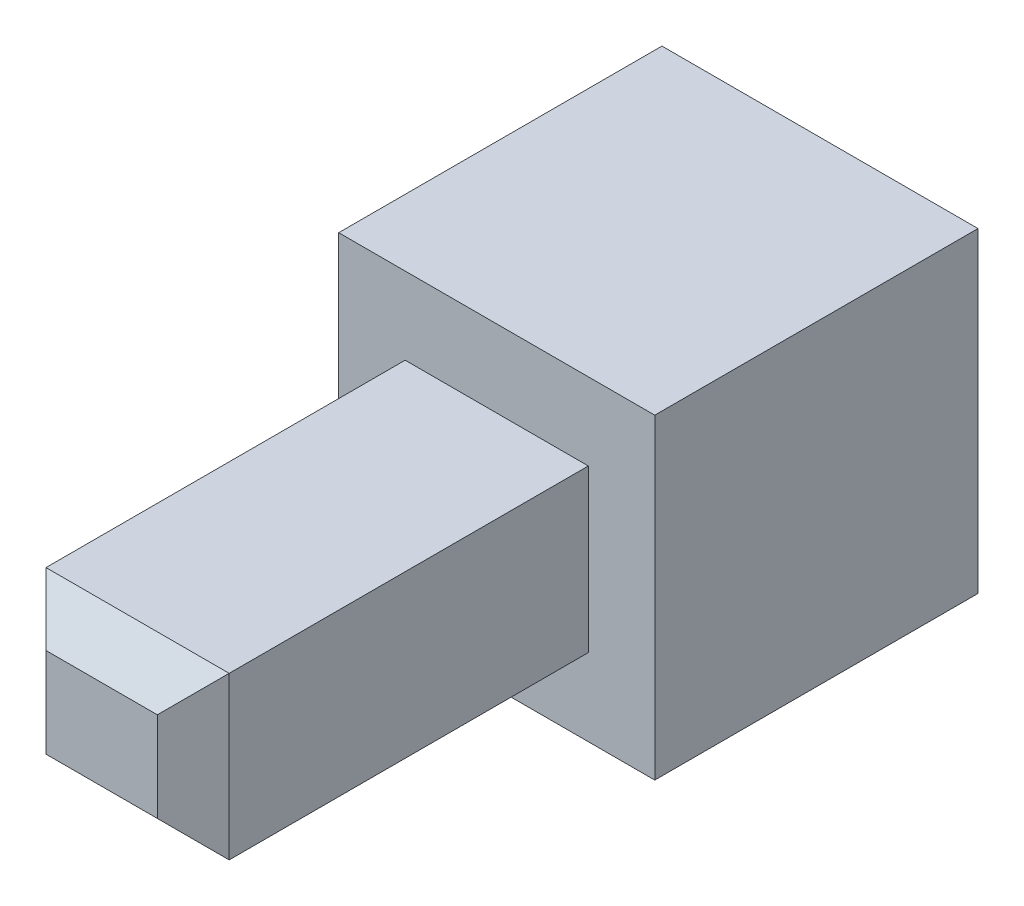
SolidWorks part; units mm, degrees
ref_plane "Front Plane" through (0, 0, 0) normal (0, 0, 1) x (1, 0, 0)
ref_plane "Top Plane" through (0, 0, 0) normal (0, 1, 0) x (1, 0, 0)
ref_plane "Right Plane" through (0, 0, 0) normal (1, 0, 0) x (0, 0, -1)
sketch "Sketch2" plane through (0, 0, -12.4) normal (0, 0, 1) x (1, 0, 0)
  line L0 (-26.1526, 94.1826) -> (-31.3526, 94.1826) construction
  line L1 (-33.1526, 95.6826) -> (-24.3526, 95.6826)
  line L2 (-33.1526, 95.6826) -> (-33.1526, 86.8826)
  line L3 (-33.1526, 86.8826) -> (-24.3526, 86.8826)
  line L4 (-24.3526, 95.6826) -> (-24.3526, 86.8826)
  line L6 (-31.6526, 93.8826) -> (-31.6526, 88.6826) construction
  line L7 (-31.3526, 88.3826) -> (-26.1526, 88.3826) construction
  line L10 (-31.9526, 94.4826) -> (-25.5526, 94.4826)
  line L11 (-31.9526, 94.4826) -> (-31.9526, 88.0826)
  line L12 (-31.9526, 88.0826) -> (-25.5526, 88.0826)
  line L13 (-25.5526, 94.4826) -> (-25.5526, 88.0826)
  dimension "D1" = 1.5
  dimension "D2" = 1.5
  dimension "D3" = 1.5
  dimension "D4" = 1.2
  dimension "D5" = 1.2
  dimension "D6" = 1.2
  dimension "D7" = 1.2
extrude "Boss-Extrude1" add sketch "Sketch2" against normal blind 2 and the other way blind 2
sketch "Sketch3" plane through (0, 0, -10.4) normal (0, 0, 1) x (1, 0, 0)
  line L1 (-33.1526, 95.6826) -> (-24.3526, 95.6826)
  line L2 (-33.1526, 95.6826) -> (-33.1526, 86.8826)
  line L3 (-33.1526, 86.8826) -> (-24.3526, 86.8826)
  line L4 (-24.3526, 95.6826) -> (-24.3526, 86.8826)
extrude "Boss-Extrude2" add sketch "Sketch3" along normal blind 5
sketch "Sketch4" plane through (0, 0, -5.4) normal (0, 0, 1) x (1, 0, 0)
  line L0 (-25.9026, 93.8326) -> (-31.6026, 93.8326) construction
  line L1 (-31.3026, 93.5326) -> (-26.2026, 93.5326)
  line L2 (-31.3026, 93.5326) -> (-31.3026, 89.0326)
  line L3 (-31.3026, 89.0326) -> (-26.2026, 89.0326)
  line L4 (-26.2026, 93.5326) -> (-26.2026, 89.0326)
  line L5 (-25.9026, 88.7326) -> (-25.9026, 93.8326) construction
  line L6 (-31.6026, 88.7326) -> (-25.9026, 88.7326) construction
  line L7 (-31.6026, 93.8326) -> (-31.6026, 88.7326) construction
  dimension "D1" = 0.3
  dimension "D2" = 0.3
  dimension "D3" = 0.3
  dimension "D4" = 0.3
extrude "Boss-Extrude3" add sketch "Sketch4" along normal blind 11
chamfer "Chamfer1" distance 1 angle 45 4 edges at (-28.7526, 93.5326, 5.6) (-26.2026, 91.2826, 5.6) (-28.7526, 89.0326, 5.6) (-31.3026, 91.2826, 5.6)
